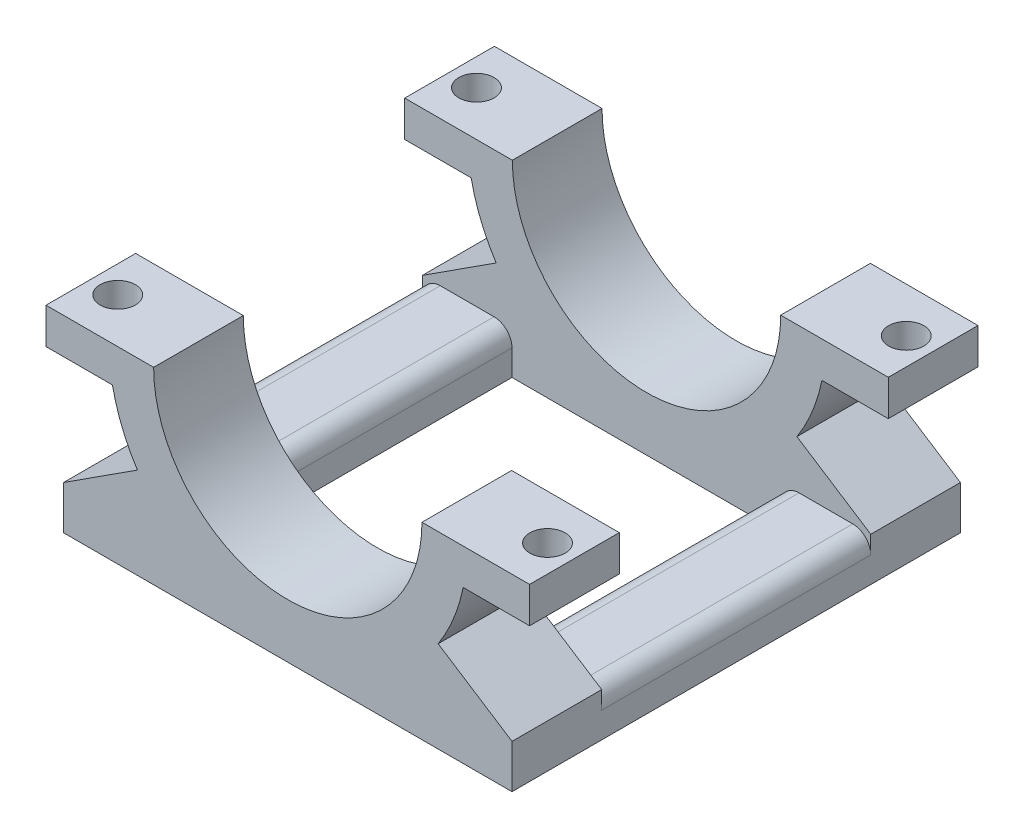
SolidWorks part; units mm, degrees
ref_plane "Front Plane" through (0, 0, 0) normal (0, 0, 1) x (1, 0, 0)
ref_plane "Top Plane" through (0, 0, 0) normal (0, 1, 0) x (1, 0, 0)
ref_plane "Right Plane" through (0, 0, 0) normal (1, 0, 0) x (0, 0, -1)
sketch "Sketch2" plane through (0, 0, 0) normal (0, 0, 1) x (1, 0, 0)
  line L0 (-6.35, 17.9075) -> (-6.35, -40.3241) construction
  line L2 (6.35, -40.3241) -> (6.35, 17.9075) construction
  line L4 (-31.75, -26.67) -> (31.75, -26.67)
  line L5 (-31.75, -26.67) -> (-31.75, -20.4978)
  line L6 (-31.75, -20.4978) -> (-21.2973, -13.7495)
  line L7 (31.75, -26.67) -> (31.75, -20.4978)
  line L8 (31.75, -20.4978) -> (21.2973, -13.7495)
  line L15 (-19, 0) -> (-25.35, 0)
  line L16 (19, 0) -> (25.35, 0)
  arc A0 (-19, 0) -> (19, 0) centre (0, 0) ccw
  arc A1 (-25.35, 0) -> (-21.2973, -13.7495) centre (0, 0) ccw
  circle A2 centre (0, 0) radius 25.35 construction
  circle A3 centre (0, 0) radius 19 construction
  arc A4 (21.2973, -13.7495) -> (25.35, 0) centre (0, 0) ccw
  dimension "D1" = 38
  dimension "D3" = 6.35
  dimension "D4" = 12.7
  dimension "D5" = 26.67
  dimension "D6" = 63.5
  dimension "D7" = 31.75
  dimension "D2" = 6.35
extrude "Boss-Extrude1" add sketch "Sketch2" along normal blind 12.7
sketch "Sketch3" plane through (0, -26.67, 0) normal (0, -1, 0) x (1, 0, 0)
  line L0 (-42.5183, 6.35) -> (38.5215, 6.35) construction
  line L1 (-31.75, 0) -> (31.75, 0) construction
  circle A0 centre (-25.4, 6.35) radius 3.81
  circle A1 centre (25.4, 6.35) radius 3.81
  dimension "D2" = 7.62
  dimension "D3" = 7.62
  dimension "D1" = 6.35
  dimension "D4" = 50.8
  dimension "D5" = 25.4
extrude "Boss-Extrude2" add sketch "Sketch3" along normal blind 2.54 draft 5
extrude "Boss-Extrude3" add sketch "Sketch2<2>" against normal blind 12.7 from offset 38.1 separate body offset against normal yes
sketch "Sketch2<2>" plane through (0, 0, 0) normal (0, 0, 1) x (1, 0, 0) same geometry as "Sketch2"
sketch "Sketch6" plane through (0, -26.67, 0) normal (0, -1, 0) x (1, 0, 0)
  line L0 (-37.6337, -44.45) -> (37.4554, -44.45) construction
  line L1 (-31.75, -38.1) -> (31.75, -38.1) construction
  line L2 (0, 19.2466) -> (0, -57.2693) construction
  circle A0 centre (-25.4, -44.45) radius 3.81
  circle A1 centre (25.4, -44.45) radius 3.81
  dimension "D2" = 7.62
  dimension "D3" = 7.62
  dimension "D1" = 6.35
  dimension "D4" = 50.8
  dimension "D5" = 25.4
extrude "Boss-Extrude4" add sketch "Sketch6" along normal blind 2.54 draft 5
sketch "Sketch7" plane through (0, 0, 12.7) normal (0, 0, 1) x (1, 0, 0)
  line L1 (-31.75, -26.67) -> (-19.05, -26.67)
  line L2 (-31.75, -26.67) -> (-31.75, -20.4978)
  line L3 (-31.75, -20.4978) -> (-19.05, -20.4978)
  line L4 (-19.05, -26.67) -> (-19.05, -20.4978)
  line L5 (31.75, -26.67) -> (19.05, -26.67)
  line L6 (31.75, -26.67) -> (31.75, -20.4978)
  line L7 (31.75, -20.4978) -> (19.05, -20.4978)
  line L8 (19.05, -26.67) -> (19.05, -20.4978)
  point P5 (0, 0)
  dimension "D1" = 38.1
extrude "Boss-Extrude5" add sketch "Sketch7" against normal through all
sketch "Sketch8" plane through (0, 0, 0) normal (0, 1, 0) x (1, 0, 0)
  line L0 (19, -12.7) -> (19, 0) construction
  line L1 (19, 0) -> (34.24, 0)
  line L2 (19, 0) -> (19, -12.7)
  line L3 (19, -12.7) -> (34.24, -12.7)
  line L4 (34.24, 0) -> (34.24, -12.7)
  line L6 (-19, 38.1) -> (-34.24, 38.1)
  line L7 (-19, 38.1) -> (-19, 50.8)
  line L8 (-19, 50.8) -> (-34.24, 50.8)
  line L9 (-34.24, 38.1) -> (-34.24, 50.8)
  line L10 (19, 38.1) -> (34.24, 38.1)
  line L11 (19, 38.1) -> (19, 50.8)
  line L12 (19, 50.8) -> (34.24, 50.8)
  line L13 (34.24, 38.1) -> (34.24, 50.8)
  line L14 (-19, 0) -> (-34.24, 0)
  line L15 (-19, 0) -> (-19, -12.7)
  line L16 (-19, -12.7) -> (-34.24, -12.7)
  line L17 (-34.24, 0) -> (-34.24, -12.7)
  dimension "D1" = 15.24
  dimension "D2" = 12.7
  dimension "D3" = 15.24
  dimension "D4" = 15.24
  dimension "D5" = 15.24
  dimension "D6" = 12.7
  dimension "D7" = 12.7
  dimension "D8" = 12.7
extrude "Boss-Extrude6" add sketch "Sketch8" against normal blind 5.08
sketch "Sketch9" plane through (0, -5.08, 0) normal (0, -1, 0) x (-1, 0, 0)
  line L0 (-44.6254, 44.45) -> (42.6991, 44.45) construction
  line L1 (-30.43, -18.4589) -> (-30.43, 59.7693) construction
  line L2 (30.43, 59.7693) -> (30.43, -18.4589) construction
  line L3 (-44.6254, -6.35) -> (42.6991, -6.35) construction
  line L4 (24.8358, 50.8) -> (34.24, 50.8) construction
  line L7 (34.24, -12.7) -> (24.8358, -12.7) construction
  line L8 (34.24, 50.8) -> (34.24, 38.1) construction
  line L9 (-34.24, 38.1) -> (-34.24, 50.8) construction
  circle A0 centre (30.43, 44.45) radius 2.5
  circle A1 centre (-30.43, 44.45) radius 2.5
  circle A2 centre (-30.43, -6.35) radius 2.5
  circle A3 centre (30.43, -6.35) radius 2.5
  dimension "D5" = 5
  dimension "D6" = 5
  dimension "D7" = 5
  dimension "D8" = 5
  dimension "D1" = 6.35
  dimension "D2" = 3.81
  dimension "D3" = 3.81
  dimension "D4" = 6.35
extrude "Cut-Extrude3" cut sketch "Sketch9" against normal blind 5.08
fillet "Fillet6" radius 2.54 4 edges at (31.75, -20.4978, -19.05) (19.05, -20.4978, -19.05) (-19.05, -20.4978, -19.05) (-31.75, -20.4978, -19.05) tangent propagation no
